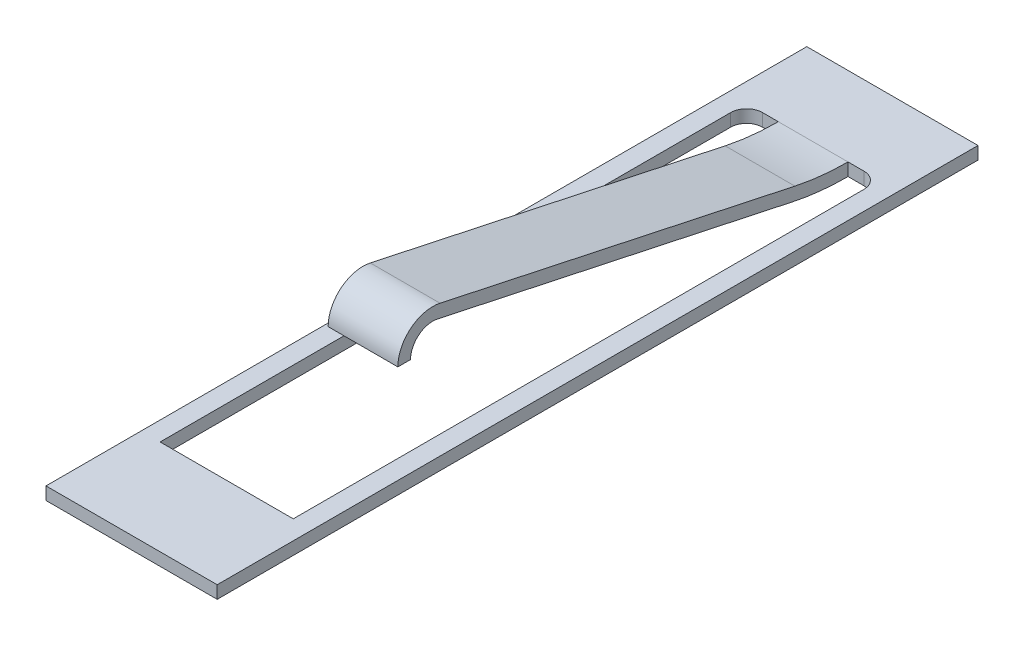
SolidWorks part; units mm, degrees
ref_plane "Front Plane" through (0, 0, 0) normal (0, 0, 1) x (1, 0, 0)
ref_plane "Top Plane" through (0, 0, 0) normal (0, 1, 0) x (1, 0, 0)
ref_plane "Right Plane" through (0, 0, 0) normal (1, 0, 0) x (0, 0, -1)
sketch "Sketch1" plane through (0, 0, 0) normal (0, 1, 0) x (1, 0, 0)
  line L0 (0, 6) -> (0, 0) construction
  line L1 (-1.35, 6) -> (1.35, 6)
  line L2 (-1.35, 6) -> (-1.35, -6)
  line L3 (-1.35, -6) -> (1.35, -6)
  line L4 (1.35, 6) -> (1.35, -6)
  line L5 (0, 0) -> (1.35, 0) construction
  line L6 (-0.55, 4.5) -> (-0.55, -2.35) construction
  line L7 (-0.55, -2.35) -> (0.55, -2.35) construction
  line L8 (0.55, -2.35) -> (0.55, 4.5) construction
  line L9 (-1.35, -1.8) -> (1.35, -1.8) construction
  line L10 (-0.8, 4.5) -> (-0.8, -6) construction
  line L11 (0.8, 4.5) -> (0.8, -6) construction
  line L12 (0.8, 4.5) -> (-0.8, 4.5) construction
  line L13 (1.05, 4.5) -> (1.05, -4.5) construction
  line L14 (1.05, -4.5) -> (-1.05, -4.5) construction
  line L15 (-1.05, -4.5) -> (-1.05, 4.5) construction
  line L16 (-0.55, -1.25) -> (0.55, -1.25) construction
  line L17 (0, -1.25) -> (0, -1.8) construction
  line L18 (0, -1.8) -> (0, -2.35) construction
  circle A0 centre (-0.8, 4.5) radius 0.25 construction
  circle A1 centre (0.8, 4.5) radius 0.25 construction
  dimension "D1" = 12
  dimension "D2" = 2.7
  dimension "D3" = 7.8
  dimension "D4" = 1.1
  dimension "D5" = 0.3
  dimension "D6" = 1.1
  dimension "D7" = 1.5
extrude "Boss-Extrude1" add sketch "Sketch1" along normal blind 0.2
sketch "Sketch2" plane through (0, 0, 0) normal (0, 1, 0) x (1, 0, 0)
  line L0 (-1.05, 4.5) -> (-1.05, -4.5)
  line L1 (-1.05, -4.5) -> (1.05, -4.5)
  line L2 (1.05, -4.5) -> (1.05, 4.5)
  line L3 (-0.8, 4.75) -> (0.8, 4.75)
  arc A0 (1.05, 4.5) -> (0.8, 4.75) centre (0.8, 4.5) ccw
  arc A2 (-1.05, 4.5) -> (-0.8, 4.75) centre (-0.8, 4.5) cw
  circle A3 centre (-0.8, 4.5) radius 0.25 construction
extrude "Cut-Extrude1" cut sketch "Sketch2" along normal through all
sketch "Sketch3" plane through (0, 0, 0) normal (1, 0, 0) x (0, 0, -1)
  line L0 (-1.8, 0) -> (-1.8, 0.95) construction
  line L1 (-2.35, 0) -> (-2.35, 0.95) construction
  line L2 (-2.35, 0.95) -> (-1.25, 0.95) construction
  line L3 (-2.35, 0) -> (-1.25, 0) construction
  line L4 (-1.8, 0.95) -> (-1.8, 1.5) construction
  line L5 (4.75, 0) -> (4.75, 0.2)
  line L6 (6, 0) -> (0, 0) construction
  line L7 (4.75, 0.2) -> (6, 0.2) construction
  line L8 (6, 0.2) -> (6, 0) construction
  line L9 (-1.6848, 1.4878) -> (3.9121, 0.2888)
  line L10 (-1.7267, 1.2922) -> (3.8702, 0.0932)
  line L11 (4.75, 0) -> (6, 0) construction
  line L12 (-2.15, 0.95) -> (-2.35, 0.95)
  circle A0 centre (-1.8, 0.95) radius 0.55 construction
  arc A1 (4.75, 0.2) -> (3.9121, 0.2888) centre (4.75, 4.2) cw
  arc A2 (4.75, 0) -> (3.8702, 0.0932) centre (4.75, 4.2) cw
  circle A3 centre (-1.8, 0.95) radius 0.35 construction
  arc A4 (-2.15, 0.95) -> (-1.7267, 1.2922) centre (-1.8, 0.95) cw
  arc A5 (-2.35, 0.95) -> (-1.6848, 1.4878) centre (-1.8, 0.95) cw
  dimension "D2" = 4
  dimension "D3" = 0.2
  dimension "D1" = 1.5
extrude "Boss-Extrude2" add sketch "Sketch3" along normal up to vertex (0.55 mm away) from vertex up to point (0.55, 0, 2.35) starting at point (-0.55, 0, 2.35)
sketch "Sketch4" plane through (0, 0, 0) normal (0, 1, 0) x (1, 0, 0)
  line L0 (-1.5, 0) -> (1.5, 0) construction
  line L1 (-1.5, 6.2) -> (1.5, 6.2)
  line L2 (-1.5, 6.2) -> (-1.5, -6.2) construction
  line L3 (-1.5, -6.2) -> (1.5, -6.2)
  line L4 (1.5, 6.2) -> (1.5, -6.2) construction
  line L5 (0, 0) -> (1.35, 0) construction
  line L6 (0, 0) -> (0, 6.2) construction
  line L7 (-1.5, -3.8) -> (1.5, -3.8)
  line L8 (-1.5, 3.8) -> (1.5, 3.8)
  line L9 (-1.5, 6.2) -> (-1.5, 3.8)
  line L10 (1.5, 3.8) -> (1.5, 6.2)
  line L11 (1.5, -3.8) -> (1.5, -6.2)
  line L12 (-1.5, -6.2) -> (-1.5, -3.8)
  dimension "D1" = 3
  dimension "D2" = 12.4
  dimension "D3" = 7.6
sketch "Sketch5" plane through (0, 0, 0) normal (1, 0, 0) x (0, 0, -1)
  line L0 (-1.5, 1.95) -> (-1.5, 0) construction
  line L1 (-1.5, 0) -> (4.75, 0) construction
  line L2 (4.75, 0) -> (6, 0) construction
  line L3 (6, 0) -> (6, 0.2) construction
  line L4 (6, 0.2) -> (4.75, 0.2) construction
  line L5 (4.75, 0.2) -> (4.75, 0) construction
  line L6 (-1.5, 1.95) -> (-1.5, 2.5) construction
  line L7 (-1.2813, 2.4546) -> (3.1592, 0.5299)
  circle A0 centre (-1.5, 1.95) radius 0.55
  circle A1 centre (-1.8, 0.95) radius 0.55 construction
  arc A2 (4.75, 0.2) -> (3.1592, 0.5299) centre (4.75, 4.2) cw
  arc A3 (3.9121, 0.2888) -> (4.75, 0.2) centre (4.75, 4.2) ccw construction
  dimension "D1" = 7.5
  dimension "D2" = 2.5
